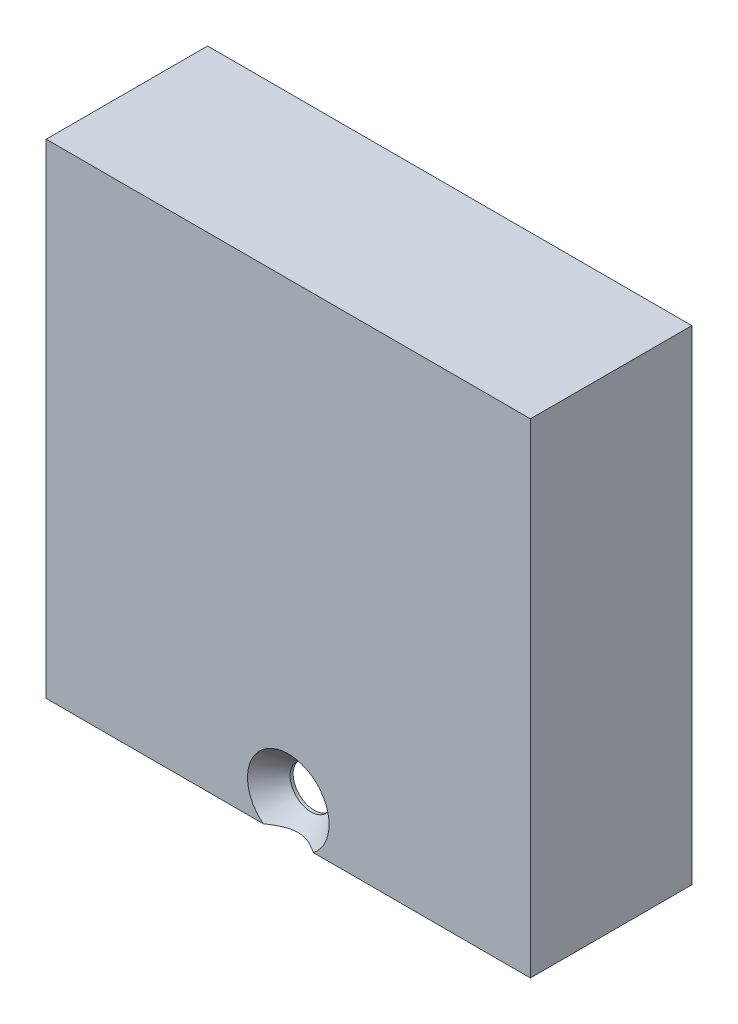
SolidWorks part; units mm, degrees
ref_plane "Plan de face" through (0, 0, 0) normal (0, 0, 1) x (1, 0, 0)
ref_plane "Plan de dessus" through (0, 0, 0) normal (0, 1, 0) x (1, 0, 0)
ref_plane "Plan de droite" through (0, 0, 0) normal (1, 0, 0) x (0, 0, -1)
sketch "Esquisse1" plane through (0, 0, 0) normal (0, 0, 1) x (1, 0, 0)
  line L1 (0, 0) -> (30, 0)
  line L2 (0, 0) -> (0, 30)
  line L3 (0, 30) -> (30, 30)
  line L4 (30, 0) -> (30, 30)
  dimension "D1" = 30
  dimension "D2" = 30
extrude "Main" add sketch "Esquisse1" along normal blind 10
sketch "Esquisse2" plane through (0, 0, 0) normal (0, -1, 0) x (1, 0, 0)
  line L0 (2.75, 0) -> (2.75, 5.2)
  line L1 (0, 0) -> (30, 0) construction
  line L2 (2.75, 5.2) -> (3.35, 5.2)
  line L3 (3.35, 5.2) -> (3.35, 6.2)
  line L4 (3.35, 6.2) -> (2.75, 6.2)
  line L5 (2.75, 6.2) -> (2.75, 8.4)
  line L6 (2.75, 8.4) -> (27.25, 8.4)
  line L7 (27.25, 8.4) -> (27.25, 6.2)
  line L8 (27.25, 6.2) -> (26.65, 6.2)
  line L9 (26.65, 6.2) -> (26.65, 5.2)
  line L10 (26.65, 5.2) -> (27.25, 5.2)
  line L11 (27.25, 5.2) -> (27.25, 0)
  line L12 (27.25, 0) -> (2.75, 0)
  line L13 (0, 10) -> (30, 10) construction
  point P13 (15, 0)
  point P18 (15, 10)
  point P19 (0, 0)
  dimension "D1" = 24.5
  dimension "D2" = 0.6
  dimension "D3" = 1
  dimension "D4" = 2.2
  dimension "D5" = 8.4
  dimension "D6" = 5.2
extrude "Main Fix" cut sketch "Esquisse2" against normal blind 28.5
sketch "Esquisse4" plane through (0, 0, 8.4) normal (0, 0, -1) x (-1, 0, 0)
  line L3 (-27.25, 28.5) -> (-27.25, 0) construction
  line L4 (-2.75, 28.5) -> (-2.75, 0) construction
  line L5 (-27.25, 15.5) -> (-27.25, 28.5)
  line L6 (-27.25, 28.5) -> (-2.75, 28.5)
  line L7 (-2.75, 28.5) -> (-2.75, 15.5)
  line L8 (-2.75, 28.5) -> (-27.25, 28.5) construction
  arc A0 (-27.25, 15.5) -> (-2.75, 15.5) centre (-15, 15.5) cw
  dimension "D1" = 12.25
  dimension "D2" = 13
extrude "Boss.-Extru.2" add sketch "Esquisse4" along normal up to surface (8.4 mm away) up to face at (15, 14.625, 0)
sketch "Esquisse5" plane through (0, 0, 5.2) normal (0, 0, -1) x (-1, 0, 0)
  line L0 (-3.35, 13.9703) -> (0, 13.9703)
  line L1 (0, 13.9703) -> (0, 30)
  line L2 (0, 30) -> (-30, 30)
  line L3 (-30, 30) -> (-30, 13.9703)
  line L4 (-30, 13.9703) -> (-26.65, 13.9703)
  line L5 (-30, 0) -> (-30, 30) construction
  line L6 (0, 30) -> (0, 0) construction
  line L7 (-30, 30) -> (0, 30) construction
  line L8 (-26.65, 19.2868) -> (-26.65, 0) construction
  arc A0 (-26.65, 13.9703) -> (-3.35, 13.9703) centre (-15, 15.5) cw
  arc A3 (-2.75, 15.5) -> (-27.25, 15.5) centre (-15, 15.5) ccw construction
  dimension "D1" = 11.75
extrude "Boss.-Extru.3" add sketch "Esquisse5" against normal up to surface (1 mm away) up to face at (26.9873, 8.7026, 6.2)
sketch "Esquisse10" plane through (0, 0, 10) normal (0, 0, 1) x (1, 0, 0)
  line L0 (0, 0) -> (30, 0) construction
  point P0 (15, 2)
  point P4 (15, 0)
  dimension "D1" = 2
hole_wizard "Fraisage pour vis à tête fraisée bombée #33" positions "Esquisse11" profile "Esquisse12" countersink size "#3" standard "Ansi Inch" end condition through all
sketch "Esquisse11" plane through (0, 0, 10) normal (0, 0, 1) x (1, 0, 0)
  point P0 (15, 2)
sketch "Esquisse12" plane through (15, 2, 10) normal (1, 0, 0) x (0, -1, 0)
  line L0 (0, 0) -> (0, 10)
  line L1 (0, 10) -> (1.3, 10)
  line L2 (1.3, 10) -> (1.3, 1.4119)
  line L3 (1.3, 1.4119) -> (2.5273, 0)
  line L5 (2.5273, 0) -> (0, 0)
  line L6 (-1.3, 1.4119) -> (-2.5273, 0) construction
  line L11 (0, -6.35) -> (0, 107.95) construction
  dimension "Diamètre du perçage jusqu'au prochain" = 2.6
  dimension "Profondeur du perçage jusqu'au prochain" = 10
  dimension "Diamètre du fraisage entrant" = 5.0546
  dimension "Angle du fraisage entrant" = 82
